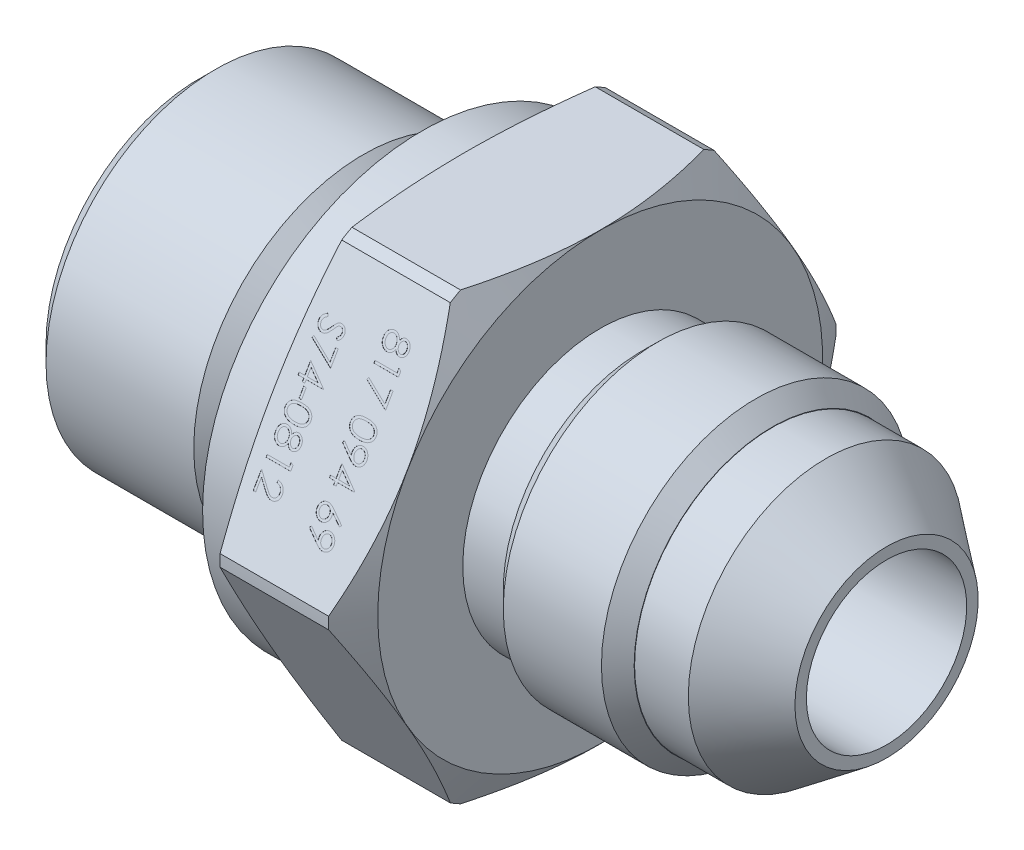
SolidWorks part; units mm, degrees
material "4140 H/T"
ref_plane "Front Plane" through (0, 0, 0) normal (0, 0, 1) x (1, 0, 0)
ref_plane "Top Plane" through (0, 0, 0) normal (0, 1, 0) x (1, 0, 0)
ref_plane "Right Plane" through (0, 0, 0) normal (1, 0, 0) x (0, 0, -1)
sketch "Sketch1" plane through (0, 0, 0) normal (0, 0, 1) x (1, 0, 0)
  line L0 (0, 0) -> (53.9967, 0) construction
  line L1 (0, 4.9) -> (0, 10.37)
  line L3 (0, 10.37) -> (10.03, 10.37)
  line L4 (13.6, 11.5) -> (15.6, 11.5)
  line L5 (16.7627, 15.5) -> (23.4, 15.5)
  line L6 (24.5, 13.5947) -> (24.5, 8.4)
  line L7 (24.5, 8.4) -> (27, 8.4)
  line L8 (27, 8.4) -> (27, 9.425)
  line L9 (27, 9.425) -> (35, 9.425)
  line L10 (35, 9.425) -> (35, 8.4)
  line L11 (35, 8.4) -> (38.2843, 8.4)
  line L12 (38.2843, 8.4) -> (42, 5.6)
  line L13 (42, 5.6) -> (42, 4.9)
  line L14 (42, 4.9) -> (0, 4.9)
  line L15 (16.2, 13.4) -> (13.6, 13.4)
  line L16 (13.6, 13.4) -> (13.6, 11.5)
  line L17 (15.6, 11.5) -> (15.6, 8.4)
  line L18 (10.03, 10.37) -> (12, 8.4)
  line L19 (12, 8.4) -> (15.6, 8.4)
  line L20 (16.7627, 15.5) -> (16.2, 13.4)
  line L21 (23.4, 15.5) -> (24.5, 13.5947)
  dimension "D1" = 11.2
  dimension "D2" = 9.8
  dimension "D3" = 16.8
  dimension "D4" = 37
  dimension "D5" = 7
  dimension "D6" = 18.85
  dimension "D7" = 15
  dimension "D8" = 10.9
  dimension "D9" = 8.3
  dimension "D10" = 42
  dimension "D11" = 20.74
  dimension "D12" = 45
  dimension "D13" = 31
  dimension "D14" = 13.6
  dimension "D15" = 26.8
  dimension "D16" = 1.1
  dimension "D17" = 30
  dimension "D18" = 75
  dimension "D19" = 2
  dimension "D20" = 23
  dimension "D21" = 12
revolve "Revolve1" add sketch "Sketch1" angle 360 about L0
cosmetic thread "Cosmetic Thread1" parameters "D2"=18.63
cosmetic thread "Cosmetic Thread2" parameters "D2"=17.42
sketch "Sketch2" plane through (24.5, 0, 0) normal (1, 0, 0) x (0, 0, -1)
  line L1 (7.852, 13.6) -> (-7.852, 13.6)
  line L2 (-7.852, 13.6) -> (-15.7039, 0)
  line L3 (-15.7039, 0) -> (-7.852, -13.6)
  line L4 (-7.852, -13.6) -> (7.852, -13.6)
  line L5 (7.852, -13.6) -> (15.7039, 0)
  line L6 (15.7039, 0) -> (7.852, 13.6)
  circle A0 centre (0, 0) radius 13.6 construction
  dimension "D1" = 27.2
extrude "Extrude1" cut sketch "Sketch2" against normal up to surface (10.9 mm away) flip side to cut up to face at (13.6, 0, 11.5)
chamfer "Chamfer1" distance 1 angle 45 1 edges at (0, 0, 10.37)
chamfer "Chamfer2" distance 1 angle 45 2 edges at (35, 0, 9.425) (27, 0, 9.425)
sketch "Sketch3" plane through (0, 6.8, 11.7779) normal (0, 0.5, 0.866) x (1, 0, 0)
  line L0 (20.7551, 7.4357) -> (20.7551, -7.4357) construction
  line L1 (23.4, 7.4357) -> (16.7627, 7.4357) construction
  line L2 (16.7627, -7.4357) -> (23.4, -7.4357) construction
  line L3 (24.5, -8.4) -> (24.5, 8.4) construction
  text T0 "817 094 69\r\nS74-0812" font "Century Gothic" height 1.5
  dimension "D1" = 3.7449
extrude "Cut-Extrude1" cut sketch "Sketch3" against normal blind 0.01
sketch "Sketch4" plane through (0, 0, 0) normal (0, 0, 1) x (1, 0, 0)
  line L0 (0, 0) -> (22.9729, 0) construction
  line L1 (15.6, 11.5) -> (15.6, -11.5) construction
  circle A0 centre (14.1, 10) radius 1.5
  dimension "D1" = 3
  dimension "D2" = 20
  dimension "D3" = 1.5
revolve "Revolve2" add sketch "Sketch4" angle 360 about L0
